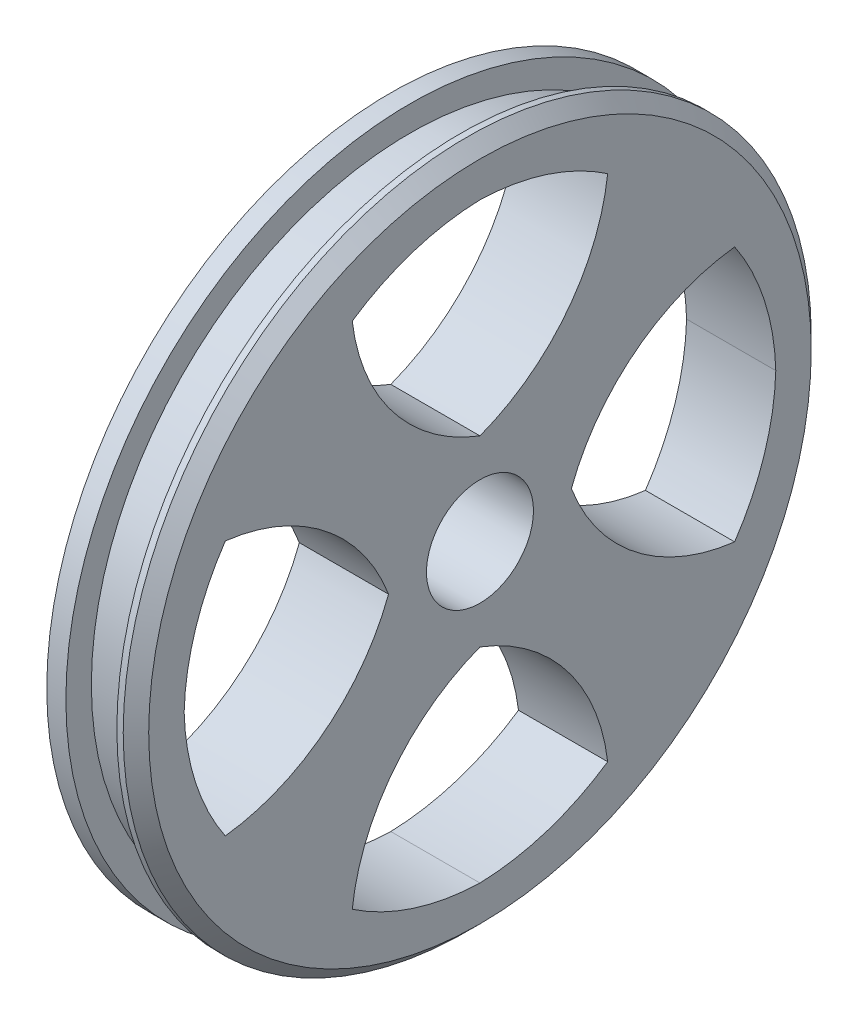
SolidWorks part; units mm, degrees
ref_plane "Front Plane" through (0, 0, 0) normal (0, 0, 1) x (1, 0, 0)
ref_plane "Top Plane" through (0, 0, 0) normal (0, 1, 0) x (1, 0, 0)
ref_plane "Right Plane" through (0, 0, 0) normal (1, 0, 0) x (0, 0, -1)
sketch "Sketch1" plane through (0, 0, 0) normal (1, 0, 0) x (0, 0, -1)
  circle A0 centre (0, 0) radius 13.5
  circle A1 centre (0, 0) radius 2.1
  dimension "D1" = 27
  dimension "D2" = 4.2
extrude "Boss-Extrude1" add sketch "Sketch1" along normal mid plane 3.5
sketch "Sketch2" plane through (0, 0, 0) normal (1, 0, 0) x (0, 0, -1)
  line L0 (0, 0) -> (0, 14.8201) construction
  arc A0 (0, 3.5875) -> (-5.0122, 9.994) centre (2.7702, 10.9187) cw
  arc A1 (-5.0122, 9.994) -> (0, 11.6087) centre (0.2591, 2.218) cw
  arc A2 (5.0122, 9.994) -> (0, 11.6087) centre (-0.2591, 2.218) ccw
  arc A3 (0, 3.5875) -> (5.0122, 9.994) centre (-2.7702, 10.9187) ccw
extrude "Cut-Extrude1" cut sketch "Sketch2" along normal through all both and the other way through all
pattern_circular "CirPattern1" count 4 over 360 about axis through (1.75, 0, 0) along (-1, 0, 0) of "Cut-Extrude1" reverse direction yes
chamfer "Chamfer1" distance 0.5 angle 45 1 edges at (1.75, 0, -13.5)
sketch "Sketch4" plane through (0, 0, 0) normal (1, 0, 0) x (0, 0, -1)
  circle A0 centre (0, 0) radius 13.5
  circle A1 centre (0, 0) radius 12.5
  circle A2 centre (0, 0) radius 13.5 construction
  dimension "D1" = 1
extrude "Cut-Extrude3" cut sketch "Sketch4" against normal mid plane 2
equation "\"axis_diameter\"=5.66"
equation "\"padding\"=0.5"
